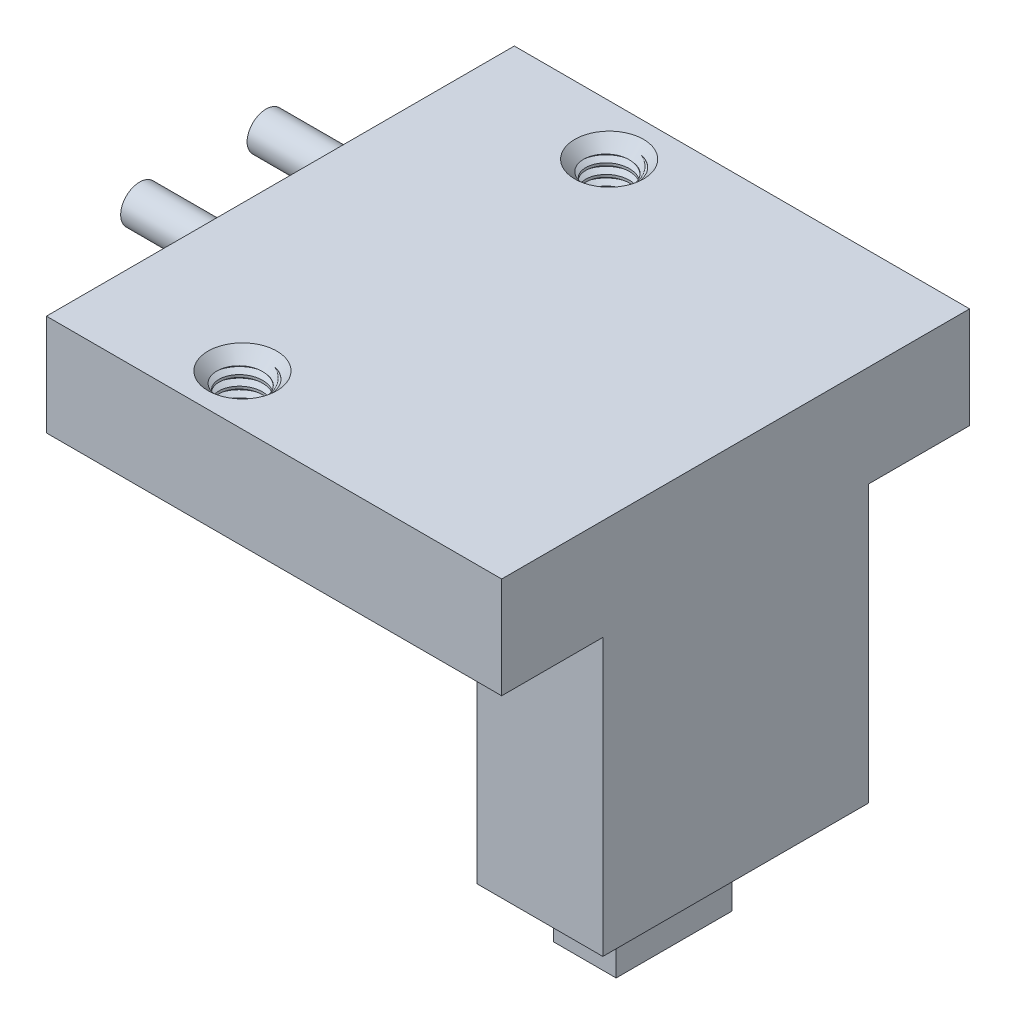
SolidWorks part; units mm, degrees
ref_plane "Front Plane" through (0, 0, 0) normal (0, 0, 1) x (1, 0, 0)
ref_plane "Top Plane" through (0, 0, 0) normal (0, 1, 0) x (1, 0, 0)
ref_plane "Right Plane" through (0, 0, 0) normal (1, 0, 0) x (0, 0, -1)
sketch "Sketch1" plane through (0, 0, 0) normal (0, 1, 0) x (1, 0, 0)
  line L1 (-13.9179, 31.2256) -> (22.0821, 31.2256)
  line L2 (-13.9179, 31.2256) -> (-13.9179, -5.7744)
  line L3 (-13.9179, -5.7744) -> (22.0821, -5.7744)
  line L4 (22.0821, 31.2256) -> (22.0821, -5.7744)
  dimension "D1" = 37
  dimension "D2" = 36
extrude "Boss-Extrude1" add sketch "Sketch1" along normal blind 5
sketch "Sketch2" plane through (0, 0, 0) normal (0, -1, 0) x (1, 0, 0)
  line L5 (-13.9179, -31.2256) -> (22.0821, -31.2256)
  line L6 (-13.9179, -31.2256) -> (-13.9179, -23.2256)
  line L7 (-13.9179, -23.2256) -> (22.0821, -23.2256)
  line L8 (22.0821, 5.7744) -> (22.0821, -31.2256) construction
  line L9 (-13.9179, 5.7744) -> (22.0821, 5.7744)
  line L10 (-13.9179, 5.7744) -> (-13.9179, -2.2256)
  line L11 (-13.9179, -2.2256) -> (22.0821, -2.2256)
  line L12 (22.0821, 5.7744) -> (22.0821, -2.2256)
  line L13 (22.0821, -31.2256) -> (22.0821, -23.2256)
  dimension "D1" = 8
  dimension "D2" = 8
extrude "Boss-Extrude2" add sketch "Sketch2" along normal blind 3
sketch "Sketch3" plane through (-13.9179, 0, 0) normal (-1, 0, 0) x (0, 0, 1)
  line L0 (-17.5956, 3) -> (-7.5956, 3) construction
  line L2 (5.7744, -3) -> (-2.2256, -3) construction
  line L5 (-2.2256, -3) -> (-2.2256, 0) construction
  circle A0 centre (-17.5956, 3) radius 1.5
  circle A1 centre (-7.5956, 3) radius 1.5
  dimension "D4" = 3
  dimension "D5" = 3
  dimension "D1" = 6
  dimension "D2" = 10
  dimension "D3" = 5.37
  dimension "D6" = 6
extrude "Boss-Extrude3" add sketch "Sketch3" along normal blind 6
sketch "Sketch5" [suppressed] plane through (0, -3, 0) normal (0, -1, 0) x (1, 0, 0)
  line L0 (22.0821, -16.1556) -> (22.0821, -9.2956) construction
  line L1 (-13.9179, -16.1556) -> (22.0821, -16.1556)
  line L2 (-13.9179, -16.1556) -> (-13.9179, -1.6556)
  line L3 (-13.9179, -1.6556) -> (22.0821, -1.6556)
  line L4 (22.0821, -16.1556) -> (22.0821, -1.6556)
  line L6 (22.0821, -23.7956) -> (-13.9179, -23.7956)
  line L7 (22.0821, -23.7956) -> (22.0821, -9.2956)
  line L8 (22.0821, -9.2956) -> (-13.9179, -9.2956)
  line L9 (-13.9179, -23.7956) -> (-13.9179, -9.2956)
  dimension "D1" = 14.5
  dimension "D2" = 14.5
sketch "Sketch18" plane through (0, 0, 0) normal (0, -1, 0) x (1, 0, 0)
  line L0 (-13.9179, -2.2256) -> (22.0821, -2.2256) construction
  line L1 (22.0821, -23.2256) -> (12.128, -23.2256)
  line L2 (22.0821, -23.2256) -> (22.0821, -2.2256)
  line L3 (22.0821, -2.2256) -> (12.128, -2.2256)
  line L4 (12.128, -23.2256) -> (12.128, -2.2256)
extrude "Boss-Extrude8" add sketch "Sketch18" along normal blind 24.85
sketch "Sketch19" plane through (0, -24.85, 0) normal (0, -1, 0) x (1, 0, 0)
  line L1 (17.0821, -8.2756) -> (12.128, -8.2756)
  line L2 (17.0821, -8.2756) -> (17.0821, -17.4256)
  line L3 (17.0821, -17.4256) -> (12.128, -17.4256)
  line L4 (12.128, -8.2756) -> (12.128, -17.4256)
  line L6 (22.0821, -2.2256) -> (12.128, -2.2256) construction
  line L7 (7.0821, -23.4756) -> (22.0821, -23.4756) construction
  dimension "D1" = 6.05
  dimension "D2" = 6.05
extrude "Boss-Extrude9" add sketch "Sketch19" along normal blind 7
extrude "Boss-Extrude4" [suppressed] add sketch "Sketch5" along normal blind 9.85
sketch "Sketch6" [suppressed] plane through (0, -3, 0) normal (0, -1, 0) x (1, 0, 0)
  line L1 (12.1663, -2.4117) -> (22.1663, -2.4117)
  line L2 (12.1663, -2.4117) -> (12.1663, -24.2717)
  line L3 (12.1663, -24.2717) -> (22.1663, -24.2717)
  line L4 (22.1663, -2.4117) -> (22.1663, -24.2717)
  dimension "D1" = 10
extrude "Boss-Extrude5" [suppressed] add sketch "Sketch6" along normal blind 9.85
sketch "Sketch7" [suppressed] plane through (0, -12.85, 0) normal (0, -1, 0) x (1, 0, 0)
  line L1 (17.6799, -8.9298) -> (11.9799, -8.9298)
  line L2 (17.6799, -8.9298) -> (17.6799, -17.7798)
  line L3 (17.6799, -17.7798) -> (11.9799, -17.7798)
  line L4 (11.9799, -8.9298) -> (11.9799, -17.7798)
  dimension "D1" = 8.85
  dimension "D2" = 5.7
extrude "Boss-Extrude6" [suppressed] add sketch "Sketch7" along normal blind 12
sketch "Sketch8" plane through (0, 5, 0) normal (0, 1, 0) x (1, 0, 0)
  line L0 (-13.9179, 31.2256) -> (-2.4179, 31.2256) construction
  line L1 (22.0821, 31.2256) -> (-13.9179, 31.2256) construction
  line L2 (-2.4179, 31.2256) -> (-2.4179, 27.2256) construction
  line L3 (-13.9179, -5.7744) -> (-2.4179, -5.7744) construction
  line L4 (-13.9179, -5.7744) -> (22.0821, -5.7744) construction
  line L5 (-2.4179, -5.7744) -> (-2.4179, -1.7744) construction
  circle A0 centre (-2.4179, 27.2256) radius 2
  circle A1 centre (-2.4179, -1.7744) radius 2
  dimension "D3" = 4
  dimension "D1" = 11.5
  dimension "D2" = 4
sketch "Sketch17" [suppressed] plane through (0, 0, 0) normal (0, -1, 0) x (1, 0, 0)
  line L1 (-13.8337, 27.1583) -> (22.1663, 27.1583)
  line L2 (-13.8337, 27.1583) -> (-13.8337, 12.0883)
  line L3 (-13.8337, 12.0883) -> (22.1663, 12.0883)
  line L4 (22.1663, 27.1583) -> (22.1663, 12.0883)
  line L5 (-13.8337, -38.7717) -> (22.1663, -38.7717)
  line L6 (-13.8337, -38.7717) -> (-13.8337, -53.8417)
  line L7 (-13.8337, -53.8417) -> (22.1663, -53.8417)
  line L8 (22.1663, -38.7717) -> (22.1663, -53.8417)
extrude "Boss-Extrude7" [suppressed] add sketch "Sketch17" along normal blind 2.05
hole_wizard "#8-32 Tapped Hole2" positions "Sketch16" profile "Sketch15" tap size "#8-32" standard "ANSI Inch"
sketch "Sketch16" plane through (0, 5, 0) normal (0, 1, 0) x (1, 0, 0)
  point P0 (-2.4179, 27.2256)
  point P3 (-2.4179, -1.7744)
sketch "Sketch15" plane through (-2.4179, 5, -27.2256) normal (1, 0, 0) x (0, 0, 1)
  line L0 (0, 0) -> (0, 12)
  line L1 (0, 12) -> (1.7272, 10.9622)
  line L2 (1.7272, 10.9622) -> (1.7272, 0.9906)
  line L3 (1.7272, 0.9906) -> (2.7178, 0)
  line L5 (2.7178, 0) -> (0, 0)
  line L6 (-1.7272, 0.9906) -> (-2.7178, 0) construction
  line L10 (0, 12) -> (-1.7272, 10.9622) construction
  line L11 (0, -6.35) -> (0, 107.95) construction
  dimension "Tap Drill Dia." = 3.4544
  dimension "Tap Drill Depth" = 12
  dimension "Near C'Sink Dia." = 5.4356
  dimension "Near C'Sink Angle" = 90
  dimension "Drill Angle" = 118
cosmetic thread "Hole Thread1" parameters "D1"=8.33, "D2"=4.1656
cosmetic thread "Hole Thread2" parameters "D1"=8.33, "D2"=4.1656
thread "Thread4" pitch 0.7937 method cut profile "Thread Profile10" start angle 0, offset 1, length 10, pitch 0.7937, diameter 3.4544
ref_plane "Plane10" through (-4.1451, 5.0094, -27.2256) normal (0, 0, 1) x (-1, 0, 0)
sketch "Thread Profile10" plane through (-4.1451, 5.0094, -27.2256) normal (0, 0, 1) x (-1, 0, 0)
  line L0 (0, 0) -> (0, 0.7937) construction
  line L1 (0, 0) -> (0.4296, 0.248)
  line L2 (0.4296, 0.248) -> (0.4296, 0.3473)
  line L3 (0.4296, 0.3473) -> (0, 0.5953)
  line L4 (0.4296, 0.2977) -> (0, 0.2977) construction
  line L11 (0, 0) -> (0, 0.5953)
  point P2 (0, 0)
  dimension "Pitch" = 0.7937
  dimension "Profile_Angle" = 60
  dimension "Profile_Land" = 0.0992
  dimension "Profile_Height" = 0.4296
thread "Thread5" pitch 0.7937 method cut profile "Thread Profile11" start angle 0, offset 1, length 10, pitch 0.7937, diameter 3.4544
ref_plane "Plane11" through (-4.1451, 5.0094, 1.7744) normal (0, 0, 1) x (-1, 0, 0)
sketch "Thread Profile11" plane through (-4.1451, 5.0094, 1.7744) normal (0, 0, 1) x (-1, 0, 0)
  line L0 (0, 0) -> (0, 0.7937) construction
  line L1 (0, 0) -> (0.4296, 0.248)
  line L2 (0.4296, 0.248) -> (0.4296, 0.3473)
  line L3 (0.4296, 0.3473) -> (0, 0.5953)
  line L4 (0.4296, 0.2977) -> (0, 0.2977) construction
  line L11 (0, 0) -> (0, 0.5953)
  point P2 (0, 0)
  dimension "Pitch" = 0.7937
  dimension "Profile_Angle" = 60
  dimension "Profile_Land" = 0.0992
  dimension "Profile_Height" = 0.4296
